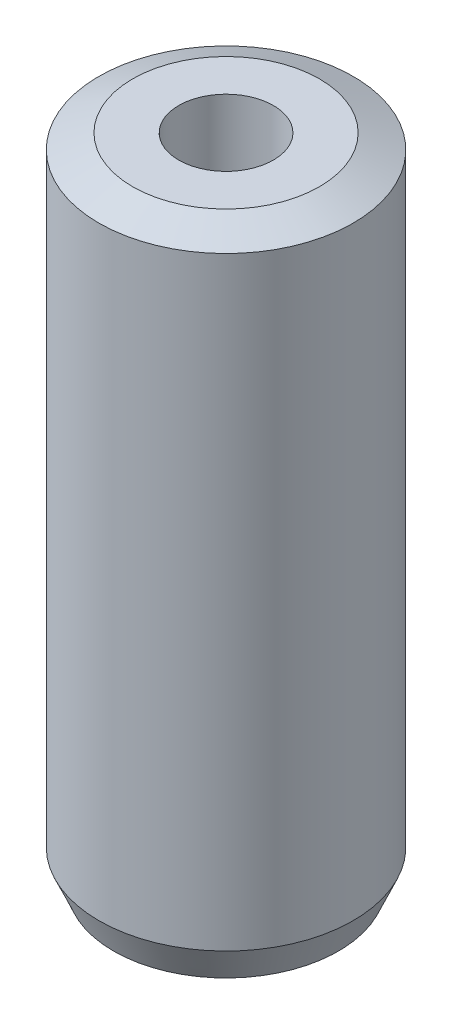
SolidWorks part; units mm, degrees
ref_plane "Front Plane" through (0, 0, 0) normal (0, 0, 1) x (1, 0, 0)
ref_plane "Top Plane" through (0, 0, 0) normal (0, 1, 0) x (1, 0, 0)
ref_plane "Right Plane" through (0, 0, 0) normal (1, 0, 0) x (0, 0, -1)
sketch "Sketch1" plane through (0, 0, 0) normal (0, 1, 0) x (1, 0, 0)
  circle A0 centre (0, 0) radius 7.5
  dimension "SHAFT_OD" = 15
extrude "Boss-Extrude1" add sketch "Sketch1" along normal blind 38.4916
sketch "Sketch2" plane through (0, 0, 0) normal (0, 1, 0) x (1, 0, 0)
  circle A0 centre (0, 0) radius 2.7913
  dimension "BORE_D" = 5.5826
extrude "Cut-Extrude1" cut sketch "Sketch2" along normal through all
chamfer "Chamfer1" distance 0.866 angle 66.468 2 edges at (0, 38.4916, 7.5) (0, 0, 7.5) first distance on face at (0, 38.4916, 7.5) first distance on face at (0, 0, 2.7913)
